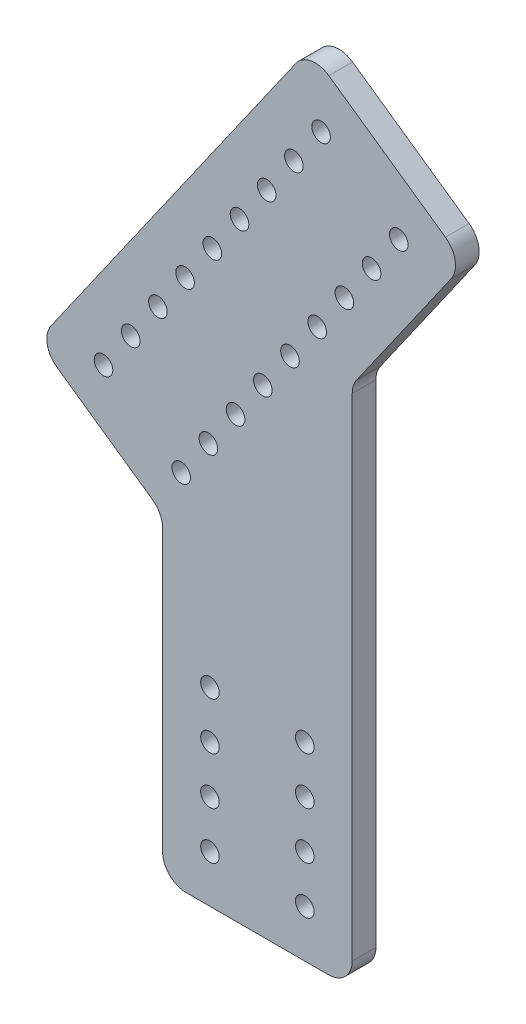
SolidWorks part; units mm, degrees
material "6061-T6 (SS)"
ref_plane "Front Plane" through (0, 0, 0) normal (0, 0, 1) x (1, 0, 0)
ref_plane "Top Plane" through (0, 0, 0) normal (0, 1, 0) x (1, 0, 0)
ref_plane "Right Plane" through (0, 0, 0) normal (1, 0, 0) x (0, 0, -1)
sketch "Sketch1" plane through (0, 0, 0) normal (0, 0, 1) x (1, 0, 0)
  line L0 (0, 156.0501) -> (50.8, 228.6)
  line L1 (0, 0) -> (50.8, 0)
  line L2 (0, 0) -> (0, 156.0501)
  line L3 (0, 228.6) -> (50.8, 228.6) construction
  line L4 (50.8, 0) -> (50.8, 228.6)
  line L5 (0, 156.0501) -> (0, 228.6) construction
  dimension "D1" = 50.8
  dimension "D2" = 55
  dimension "D3" = 228.6
extrude "Boss-Extrude1" add sketch "Sketch1" along normal blind 6.35
sketch "Sketch2" plane through (0, 0, 0) normal (0, 0, -1) x (-1, 0, 0)
  line L0 (-50.8, 0) -> (-50.8, 228.6) construction
  line L1 (-50.8, 0) -> (-50.8, 228.6) construction
  line L2 (-50.8, 12.7) -> (0, 12.7) construction
  line L3 (-50.8, 0) -> (-50.8, 228.6) construction
  line L4 (0, 156.0501) -> (0, 0) construction
  line L5 (0, 0) -> (-50.8, 0) construction
  line L6 (-50.8, 228.6) -> (-92.4129, 199.4623) construction
  line L7 (-50.8, 228.6) -> (0, 156.0501)
  line L8 (-92.4129, 199.4623) -> (-41.6129, 126.9124) construction
  line L9 (0, 156.0501) -> (-41.6129, 126.9124) construction
  line L10 (-50.8, 228.6) -> (0, 156.0501) construction
  line L11 (-88.2447, 193.5095) -> (-46.6318, 222.6472) construction
  line L12 (-39.3474, 212.244) -> (-50.8, 204.2248)
  circle A33 centre (-38.1, 12.7) radius 2.4892
  circle A34 centre (-12.7, 12.7) radius 2.4892
  circle A35 centre (-12.7, 25.4) radius 2.4892
  circle A36 centre (-38.1, 25.4) radius 2.4892
  circle A37 centre (-12.7, 38.1) radius 2.4892
  circle A38 centre (-38.1, 38.1) radius 2.4892
  circle A39 centre (-12.7, 50.8) radius 2.4892
  circle A40 centre (-38.1, 50.8) radius 2.4892
  circle A41 centre (-12.7, 63.5) radius 2.4892
  circle A42 centre (-38.1, 63.5) radius 2.4892
  circle A43 centre (-77.8415, 200.7939) radius 2.4892 construction
  circle A44 centre (-57.035, 215.3628) radius 2.4892 construction
  circle A45 centre (-49.7506, 204.9596) radius 2.4892 construction
  circle A46 centre (-70.5571, 190.3907) radius 2.4892 construction
  circle A47 centre (-42.4662, 194.5563) radius 2.4892
  circle A48 centre (-63.2727, 179.9875) radius 2.4892
  circle A49 centre (-35.1818, 184.1531) radius 2.4892
  circle A50 centre (-55.9882, 169.5843) radius 2.4892
  circle A51 centre (-27.8974, 173.7499) radius 2.4892
  circle A52 centre (-48.7038, 159.181) radius 2.4892
  circle A53 centre (-20.6129, 163.3466) radius 2.4892
  circle A54 centre (-41.4194, 148.7778) radius 2.4892
  circle A55 centre (-13.3285, 152.9434) radius 2.4892
  circle A56 centre (-34.135, 138.3746) radius 2.4892
  circle A57 centre (-6.0441, 142.5402) radius 2.4892
  circle A58 centre (-26.8506, 127.9713) radius 2.4892
  circle A59 centre (1.2403, 132.1369) radius 2.4892
  circle A60 centre (-19.5661, 117.5681) radius 2.4892
  circle A61 centre (8.5247, 121.7337) radius 2.4892
  circle A62 centre (-12.2817, 107.1649) radius 2.4892
  circle A63 centre (15.8092, 111.3305) radius 2.4892
  circle A64 centre (-4.9973, 96.7616) radius 2.4892
  circle A65 centre (23.0936, 100.9272) radius 2.4892 construction
  circle A66 centre (2.2871, 86.3584) radius 2.4892 construction
  point P87 (0, 0)
  line M1 (0, 0) -> (0, 156.0501)
  line M3 (-50.8, 228.6) -> (-50.8, 0)
  dimension "D1" = 12.7
  dimension "D2" = 25.4
  dimension "D3" = 4.9784
  dimension "D4" = 12.7
  dimension "D5" = 12.7
  dimension "D6" = 50.8
  dimension "D8" = 12.7
  dimension "D9" = 25.4
  dimension "D10" = 7.267
  dimension "D11" = 12.7
  dimension "D13" = 12.7
  dimension "D7" = 5
  dimension "D12" = 12
extrude "Cut-Extrude1" cut sketch "Sketch2" against normal through all contours L12 L7 M3 | A47 | A49 | A51 | A53 | A55 | A57 | A58 | A60 | A62 | A56 | A54 | A64 | A33 | A34 | A35 | A36 | A38 | A37 | A39 | A40 region at (46.9825, 215.0229, 0) region at (38.1, 12.7, 0) region at (12.7, 12.7, 0) region at (12.7, 25.4, 0) region at (38.1, 25.4, 0) region at (12.7, 38.1, 0) region at (38.1, 38.1, 0) region at (12.7, 50.8, 0) region at (38.1, 50.8, 0) region at (42.4662, 194.5563, 0) region at (35.1818, 184.1531, 0) region at (27.8974, 173.7499, 0) region at (20.6129, 163.3466, 0) region at (41.4194, 148.7778, 0) region at (13.3285, 152.9434, 0) region at (34.135, 138.3746, 0) region at (6.0441, 142.5402, 0) region at (26.8506, 127.9713, 0) region at (19.5661, 117.5681, 0) region at (12.2817, 107.1649, 0) region at (4.9973, 96.7616, 0)
sketch "Sketch3" plane through (0, 0, 0) normal (0, 0, 1) x (1, 0, 0)
  line L0 (-33.4968, 108.2117) -> (8.1161, 79.074)
  line L1 (-33.4968, 108.2117) -> (39.3474, 212.244)
  line L2 (8.1161, 79.074) -> (80.9603, 183.1063)
  line L3 (39.3474, 212.244) -> (80.9603, 183.1063)
  line L4 (39.3474, 212.244) -> (0, 156.0501) construction
  line L5 (0, 156.0501) -> (0, 0) construction
  line L6 (0, 156.0501) -> (0, 0)
  line L7 (50.8, 0) -> (50.8, 204.2248) construction
  line L8 (50.8, 0) -> (50.8, 204.2248)
  circle A0 centre (42.4662, 194.5563) radius 2.4892 construction
  circle A1 centre (4.9973, 96.7616) radius 2.4892 construction
  dimension "D1" = 50.8
  dimension "D2" = 12.7
  dimension "D3" = 12.7
extrude "Boss-Extrude2" add sketch "Sketch3" along normal up to surface (6.35 mm away) contours L6 L1 L0 | L8 L2 L3 region at (-11.1656, 116.3396, 0) region at (60.8534, 175.788, 0) up to face at (35.6108, 25.4, 6.35)
extrude "Cut-Extrude2" cut sketch "Sketch2<4>" against normal through all contours A63 | A61 | A59 M1 | A52 M3 | A50 | A59 M1 | A52 M3 | A48 region at (-1.6688, 132.1369, 0) region at (0.5121, 132.1369, 0) region at (48.6178, 159.181, 0) region at (50.9583, 159.181, 0) region at (63.2727, 179.9875, 0) region at (55.9882, 169.5843, 0) region at (-8.5247, 121.7337, 0) region at (-15.8092, 111.3305, 0)
sketch "Sketch2<4>" plane through (0, 0, 0) normal (0, 0, -1) x (-1, 0, 0) same geometry as "Sketch2"
fillet "Fillet1" radius 6.35 7 edges at (50.8, 0, 3.175) (0, 0, 3.175) (80.9603, 183.1063, 3.175) (50.8, 140.0329, 3.175) (0, 84.7569, 3.175) (39.3474, 212.244, 3.175) (-33.4968, 108.2117, 3.175)
